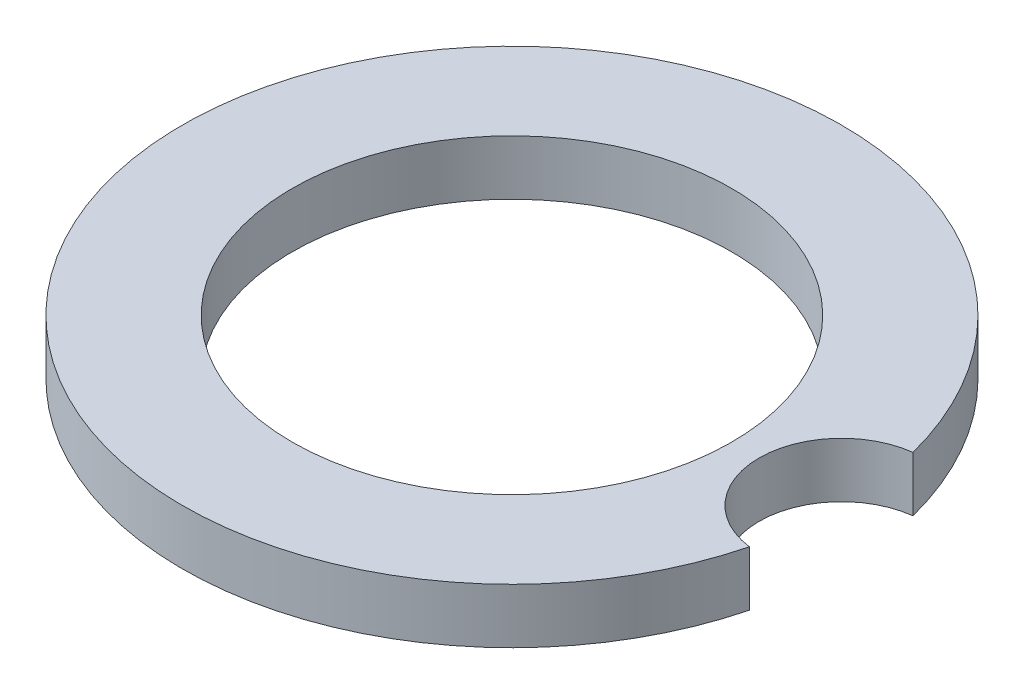
SolidWorks part; units mm, degrees
ref_plane "Front Plane" through (0, 0, 0) normal (0, 0, 1) x (1, 0, 0)
ref_plane "Top Plane" through (0, 0, 0) normal (0, 1, 0) x (1, 0, 0)
ref_plane "Right Plane" through (0, 0, 0) normal (1, 0, 0) x (0, 0, -1)
sketch "Sketch1" plane through (0, 0, 0) normal (0, 1, 0) x (1, 0, 0)
  circle A0 centre (0, 0) radius 50.8
  circle A1 centre (0, 0) radius 76.1746
  dimension "Front_CR_ID" = 101.6
  dimension "Front_CR_OD" = 152.3492
extrude "Boss-Extrude1" add sketch "Sketch1" along normal blind 12.7 contours A1
extrude "Cut-Extrude2" cut sketch "Sketch1<10>" along normal through all contours A0
sketch "Sketch1<10>" plane through (0, 0, 0) normal (0, 1, 0) x (1, 0, 0) same geometry as "Sketch1"
sketch "Sketch2" plane through (0, 12.7, 0) normal (0, 1, 0) x (1, 0, 0)
  line L0 (76.2, 19.05) -> (76.2, -19.05)
  arc A0 (76.2, 19.05) -> (76.2, -19.05) centre (76.1746, 0) ccw
  circle A1 centre (0, 0) radius 76.1746 construction
  dimension "D1" = 38.1
extrude "Cut-Extrude3" cut sketch "Sketch2" against normal through all contours A0 L0
ref_plane "Plane1" through (0, 6.35, 0) normal (0, -1, 0) x (-1, 0, 0)
equation "\"Bodytube_OD\" = 6.17in"
equation "\"Bodytube_ID\" = 5.998in"
equation "\"Motor_OD\" = 4in"
equation "\"Fwd_Tube_Length\" = 40in"
equation "\"Mid_Tube_Length\" = 1in"
equation "\"Aft_Section_Length\"= 39in"
equation "\"Mid_Coupler_Length\"= 13in"
equation "\"Aft_Lower_Length\"= 22in"
equation "\"AB_Coupler_OD_Length\"= 1in"
equation "\"AB_Coupling_Section_Length\"= 0.375in"
equation "\"AB_Coupler_Length\"= \"AB_Coupler_OD_Length\" + \"AB_Coupling_Section_Length\" * 2"
equation "\"Cutout_Angle\" = 80"
equation "\"AB_Paddle_Height\" = 0.375in"
equation "\"AB_Coupler_Num_Screws\"= 6"
equation "\"Num_Cutouts\" = 3"
equation "\"AB_Coupler_OD\"= 6.17in"
equation "\"AB_Coupler_ID\"= 5.75in"
equation "\"AB_Coupler_Surface_Diameter\"= 5.998in"
equation "\"AB_Coupling_Screw_Diameter\"= 0.1065in"
equation "\"AB_Central_Bushing_Length\" = .75in"
equation "\"Lead_Screw_Dist\" = 2.25in"
equation "\"Lead_Screw_Diam\" = 11mm"
equation "\"Lead_Screw_Length\" = (\"Mid_Coupler_Length\" + 2*0.375in + 2*0.5in)"
equation "\"Paddle_Pin_Offset\" = .25in"
equation "\"Paddle_Pin_Radius\" = 2.25in"
equation "\"Paddle_Gear_OD\" = 3.2in"
equation "\"Fwd_BKHD_From_Top\" = 18in"
equation "\"Front_CR_OD@Sketch1\"=\"Bodytube_ID\""
equation "\"Front_CR_ID@Sketch1\"=\"Motor_OD\""
